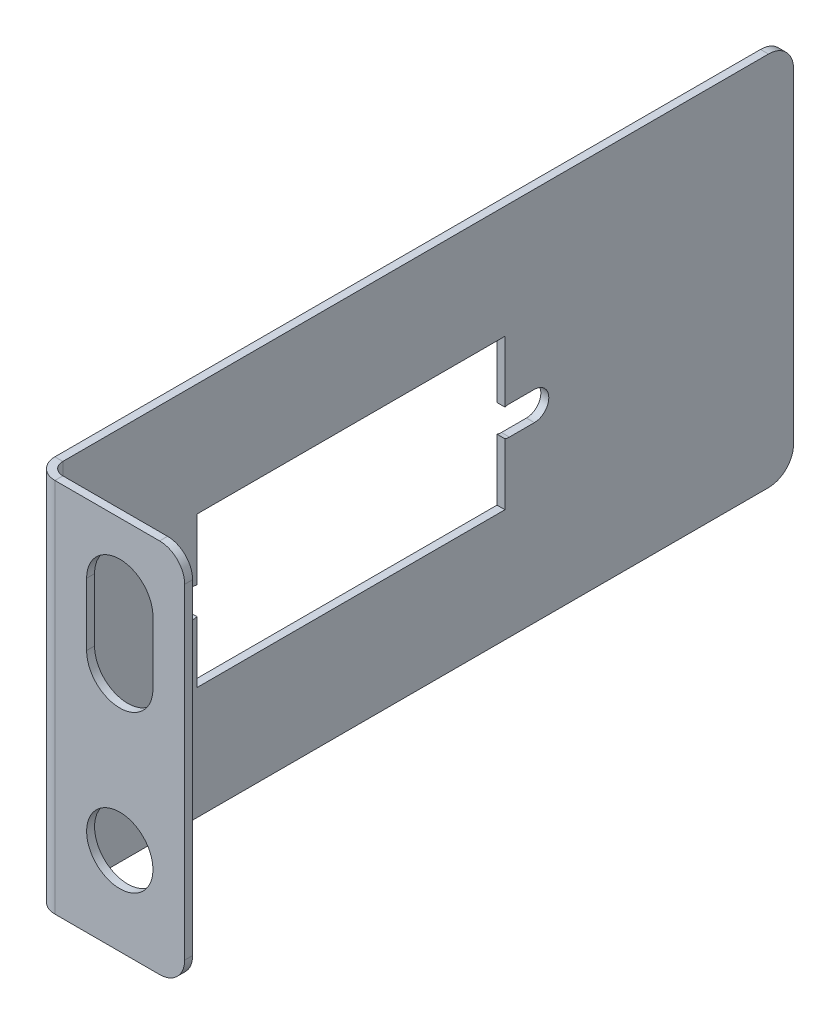
SolidWorks part; units mm, degrees
note: The reader was unsure of these and kept them because the rebuilt part matched: flange length of "Edge-Flange1".
ref_plane "Front Plane" through (0, 0, 0) normal (0, 0, 1) x (1, 0, 0)
ref_plane "Top Plane" through (0, 0, 0) normal (0, 1, 0) x (1, 0, 0)
ref_plane "Right Plane" through (0, 0, 0) normal (1, 0, 0) x (0, 0, -1)
sketch "Sketch1" plane through (0, 0, 0) normal (1, 0, 0) x (0, 0, -1)
  line L1 (-30, 15) -> (30, 15)
  line L2 (-30, 15) -> (-30, -15)
  line L3 (-30, -15) -> (30, -15)
  line L4 (30, 15) -> (30, -15)
  line L5 (-30, 15) -> (30, -15) construction
  line L6 (-30, -15) -> (30, 15) construction
  point P0 (0, 0)
  dimension "D1" = 60
  dimension "D2" = 30
base flange "Base-Flange1" sketch "Sketch1" thickness 0.635 reverse thickness direction no parameters "D1"=1
sketch "Sketch9" plane through (0, 0, 0) normal (1, 0, 0) x (0, 0, -1)
  line L0 (6.95, -6) -> (6.95, 6)
  line L2 (-17.65, -6) -> (-17.65, 6)
  line L4 (-17.65, 6) -> (6.95, 6)
  line L5 (-17.65, -6) -> (6.95, -6)
  line L6 (5.9, -5.9) -> (5.9, 5.9) construction
  line L7 (5.9, 5.9) -> (-16.6, 5.9) construction
  point P0 (5.9, 0)
  point P3 (-5.35, 6)
  point P7 (-5.35, 5.9)
  point P12 (6.95, 0)
  dimension "D1" = 12
  dimension "D2" = 24.6
extrude "Cut-Extrude1" cut sketch "Sketch9" against normal through all normal cut yes
sketch "Sketch10" plane through (-0.635, 0, 0) normal (-1, 0, 0) x (0, 0, 1)
  line L0 (-9.3, 0) -> (-7.3, 0) construction
  line L3 (-9.3, 1.15) -> (-7.3, 1.15)
  line L6 (-9.3, -1.15) -> (-7.3, -1.15)
  line L8 (18, 0) -> (20, 0) construction
  line L9 (18, 1.15) -> (20, 1.15)
  line L10 (18, -1.15) -> (20, -1.15)
  arc A4 (-9.3, 1.15) -> (-9.3, -1.15) centre (-9.3, 0) ccw
  arc A5 (-7.3, -1.15) -> (-7.3, 1.15) centre (-7.3, 0) ccw
  arc A6 (18, 1.15) -> (18, -1.15) centre (18, 0) ccw
  arc A7 (20, -1.15) -> (20, 1.15) centre (20, 0) ccw
  point P0 (-8.3, 0)
  point P1 (19, 0)
  point P4 (-8.3, 0)
  point P11 (19, 0)
  dimension "D2" = 2.3
  dimension "D1" = 2
  dimension "D3" = 2.3
  dimension "D4" = 2
extrude "Cut-Extrude2" cut sketch "Sketch10" against normal through all normal cut yes
edge flange "Edge-Flange1" sketch "Sketch13" flange angle 90 flange length 12 flange position material inside bend radius 1 thickness 0.635 relief rectangular parameters "D6"=10
sketch "Sketch13" plane through (0, 0, 30) normal (0, 0, 1) x (0, -1, 0)
  line L0 (-15, 0) -> (15, 0) construction
  line L1 (-15, 0) -> (15, 0)
  line L2 (-15, 0) -> (-15, 11.365)
  line L3 (-15, 11.365) -> (15, 11.365)
  line L4 (15, 11.365) -> (15, 0)
bend "EdgeBend1" bend radius 1 bend angle 90 parameters "D5"=1
sketch "Sketch14" plane through (0, 0, 29.365) normal (0, 0, -1) x (-1, 0, 0)
  line L0 (-6.1825, 15) -> (-6.1825, -15) construction
  line L1 (-6.1825, 4.5) -> (-6.1825, 9.5) construction
  line L2 (-8.8325, 4.5) -> (-8.8325, 9.5)
  line L3 (-3.5325, 4.5) -> (-3.5325, 9.5)
  line L4 (-11.365, 15) -> (-1, 15) construction
  line L5 (-1, -15) -> (-11.365, -15) construction
  circle A0 centre (-6.1825, -8) radius 2.65
  arc A1 (-8.8325, 4.5) -> (-3.5325, 4.5) centre (-6.1825, 4.5) ccw
  arc A2 (-3.5325, 9.5) -> (-8.8325, 9.5) centre (-6.1825, 9.5) ccw
  point P6 (-6.1825, 7)
  point P11 (-6.1825, 15)
  dimension "D3" = 5.3
  dimension "D1" = 5
  dimension "D2" = 5.3
  dimension "D4" = 8
  dimension "D5" = 7
extrude "Cut-Extrude3" cut sketch "Sketch14" against normal through all normal cut yes
fillet "Fillet1" radius 2 4 edges at (11.365, 15, 29.6825) (11.365, -15, 29.6825) (-0.3175, -15, -30) (-0.3175, 15, -30)
sketch "Bend-Lines1" [suppressed] plane through (0, 0, 0) normal (0, 1, 0) x (1, 0, 0)
sketch "Bounding-Box1" [suppressed] plane through (0, 0, 0) normal (0, 1, 0) x (1, 0, 0)
sheet metal parameters "Sheet-Metal1" thickness 0.635 parameters "D1"=1
flat pattern "Flat-Pattern1" [suppressed]
sketch "Bend-Lines2" plane through (0, 0, 0) normal (0, 1, 0) x (1, 0, 0)
sketch3d "Bounding-Box2" [suppressed]
  line L0 (25.4, -20, 0) -> (-25.4, -20, 0) construction
  line L1 (25.4, 20, 0) -> (-25.4, 20, 0) construction
  line L2 (25.4, -20, 0) -> (25.4, 20, 0) construction
  line L3 (-25.4, -20, 0) -> (-25.4, 20, 0) construction
sheet metal parameters "Sheet-Metal3" thickness 0.635 parameters "D1"=1
flat pattern "Flat-Pattern1"
sketch "Bend-Lines2" plane through (0, 0, 0) normal (1, 0, 0) x (0, 0, -1)
  line L0 (-25.4, -19.3998) -> (25.4, -19.3998) construction
  line L1 (-25.4, -19.3998) -> (25.4, -19.3998) construction
sketch3d "Bounding-Box2" [suppressed]
  line L0 (-25.4, -30.7995, 0) -> (25.4, -30.7995, 0) construction
  line L1 (-25.4, 20, 0) -> (25.4, 20, 0) construction
  line L2 (-25.4, -30.7995, 0) -> (-25.4, 20, 0) construction
  line L3 (25.4, -30.7995, 0) -> (25.4, 20, 0) construction
sheet metal parameters "Sheet-Metal4" thickness 0.635 parameters "D1"=1
flat pattern "Flat-Pattern1"
sketch "Bend-Lines2" plane through (0, 0, 0) normal (1, 0, 0) x (0, 0, -1)
sketch3d "Bounding-Box2" [suppressed]
  line L0 (-30, -15, 0) -> (30, -15, 0) construction
  line L1 (-30, 15, 0) -> (30, 15, 0) construction
  line L2 (-30, -15, 0) -> (-30, 15, 0) construction
  line L3 (30, -15, 0) -> (30, 15, 0) construction
sheet metal parameters "Sheet-Metal6" thickness 0.635 parameters "D1"=1
flat pattern "Flat-Pattern1"
sketch "Bend-Lines2" plane through (0, 0, 0) normal (1, 0, 0) x (0, 0, -1)
  line L0 (-29.3998, 15) -> (-29.3998, -15) construction
  line L1 (-29.3998, 15) -> (-29.3998, -15) construction
sketch3d "Bounding-Box2" [suppressed]
  line L0 (-40.7995, -15, 0) -> (30, -15, 0) construction
  line L1 (-40.7995, 15, 0) -> (30, 15, 0) construction
  line L2 (-40.7995, -15, 0) -> (-40.7995, 15, 0) construction
  line L3 (30, -15, 0) -> (30, 15, 0) construction
bend of the flat pattern "Flatten-<EdgeBend1>1"
sheet metal parameters "Sheet-Metal7" thickness 0.635 parameters "D1"=1
flat pattern "Flat-Pattern1"
sketch "Bend-Lines2" plane through (0, 0, 0) normal (1, 0, 0) x (0, 0, -1)
  line L0 (-29.3998, 15) -> (-29.3998, -15) construction
  line L1 (-29.3998, 15) -> (-29.3998, -15) construction
sketch3d "Bounding-Box2" [suppressed]
  line L0 (-40.7995, 15, 0) -> (30, 15, 0) construction
  line L1 (-40.7995, -15, 0) -> (30, -15, 0) construction
  line L2 (-40.7995, 15, 0) -> (-40.7995, -15, 0) construction
  line L3 (30, 15, 0) -> (30, -15, 0) construction
bend of the flat pattern "Flatten-<EdgeBend1>1"
